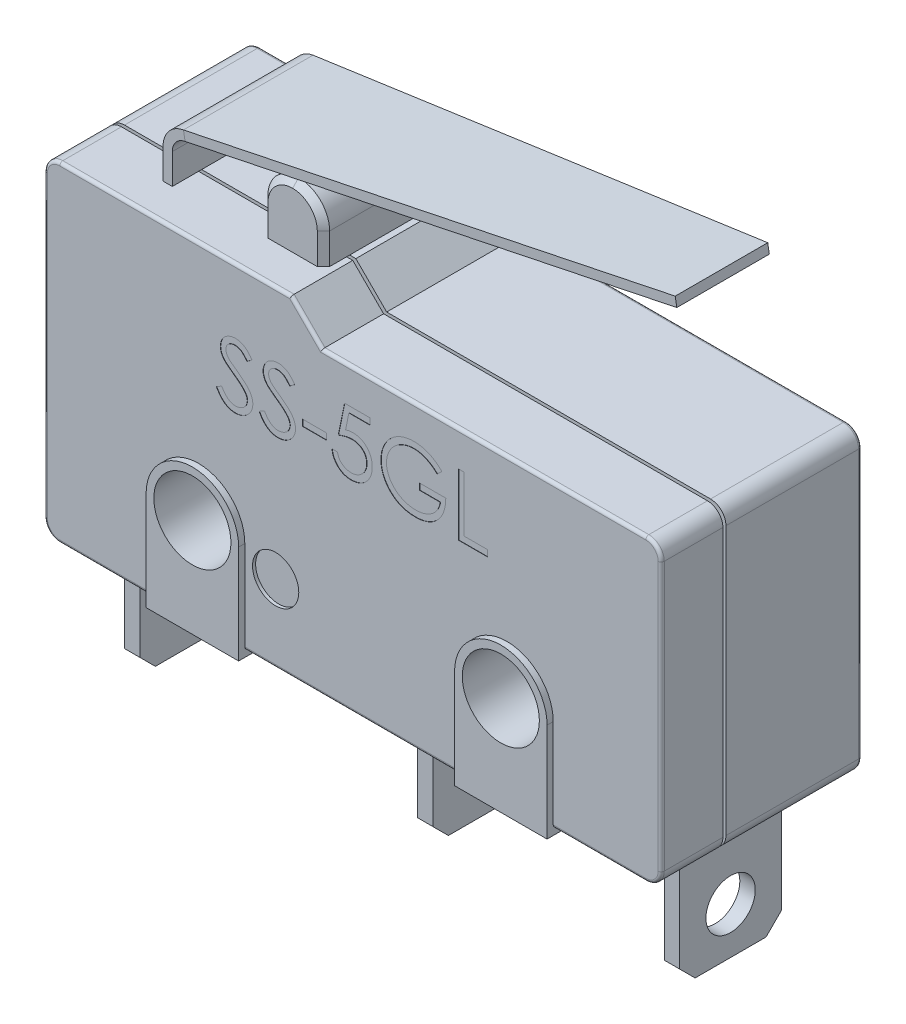
SolidWorks part; units mm, degrees
ref_plane "前基準面" through (0, 0, 0) normal (0, 0, 1) x (1, 0, 0)
ref_plane "上基準面" through (0, 0, 0) normal (0, 1, 0) x (1, 0, 0)
ref_plane "右基準面" through (0, 0, 0) normal (1, 0, 0) x (0, 0, -1)
sketch "草圖1" plane through (0, 0, 0) normal (0, 0, 1) x (1, 0, 0)
  line L0 (9, 9.7) -> (8, 10.7)
  line L1 (0, 0) -> (20, 0)
  line L2 (0, 0) -> (0, 10.7)
  line L3 (0, 10.7) -> (8, 10.7)
  line L4 (20, 0) -> (20, 10.7)
  line L7 (9, 9.7) -> (20, 9.7)
  line L8 (20, 10.7) -> (20, 9.7)
  dimension "D1" = 20
  dimension "D2" = 10.7
  dimension "D3" = 1
  dimension "D4" = 9
  dimension "D5" = 135
extrude "填料-伸長1" add sketch "草圖1" along normal blind 6.5 contours L7 L0 L3 L2 L1 L4 region at (9.7588, 5.0742, 0)
sketch "草圖2" plane through (0, 0, 6.5) normal (0, 0, 1) x (1, 0, 0)
  line L0 (0, 0) -> (0, 10.7) construction
  line L1 (0, 0) -> (20, 0) construction
  circle A0 centre (5, 3) radius 1.25
  circle A1 centre (15, 3) radius 1.25
  dimension "D1" = 2.5
  dimension "D2" = 10
  dimension "D3" = 5
  dimension "D4" = 3
extrude "除料-伸長1" cut sketch "草圖2" against normal through all
sketch "草圖3" plane through (0, 0, 6.5) normal (0, 0, 1) x (1, 0, 0)
  line L0 (0, 0) -> (20, 0) construction
  line L2 (3.5, 3) -> (3.5, 0)
  line L3 (3.5, 0) -> (6.5, 0)
  line L4 (6.5, 3) -> (6.5, 0)
  line L7 (13.5, 3) -> (13.5, 0)
  line L8 (13.5, 0) -> (16.5, 0)
  line L9 (16.5, 3) -> (16.5, 0)
  arc A0 (6.5, 3) -> (3.5, 3) centre (5, 3) ccw
  arc A1 (16.5, 3) -> (13.5, 3) centre (15, 3) ccw
  circle A2 centre (5, 3) radius 1.25
  circle A3 centre (15, 3) radius 1.25
  dimension "D1" = 3
  dimension "D2" = 2.5
extrude "填料-伸長2" add sketch "草圖3" along normal blind 0.2
sketch "草圖4" plane through (0, 0, 0) normal (0, 0, -1) x (-1, 0, 0)
  line L0 (0, 0) -> (-20, 0) construction
  line L2 (-16.5, 3) -> (-16.5, 0)
  line L3 (-16.5, 0) -> (-13.5, 0)
  line L4 (-13.5, 3) -> (-13.5, 0)
  line L6 (-6.5, 3) -> (-6.5, 0)
  line L7 (-6.5, 0) -> (-3.5, 0)
  line L8 (-3.5, 3) -> (-3.5, 0)
  arc A0 (-13.5, 3) -> (-16.5, 3) centre (-15, 3) ccw
  arc A1 (-3.5, 3) -> (-6.5, 3) centre (-5, 3) ccw
  circle A2 centre (-15, 3) radius 1.25
  circle A3 centre (-5, 3) radius 1.25
  dimension "D1" = 3
  dimension "D2" = 2.5
extrude "填料-伸長3" add sketch "草圖4" along normal blind 0.2
sketch "草圖5" plane through (0, 10.7, 0) normal (0, 1, 0) x (1, 0, 0)
  line L0 (0, -6.5) -> (0, 0) construction
  line L1 (5.8, -1.25) -> (7.8, -1.25)
  line L2 (5.8, -1.25) -> (5.8, -5.25)
  line L3 (5.8, -5.25) -> (7.8, -5.25)
  line L4 (7.8, -1.25) -> (7.8, -5.25)
  line L5 (0, 0) -> (8, 0) construction
  dimension "D1" = 2
  dimension "D2" = 5.8
  dimension "D3" = 4
  dimension "D4" = 1.25
extrude "填料-伸長4" add sketch "草圖5" along normal blind 2 separate body
fillet "圓角1" radius 1 2 edges at (5.8, 12.7, 3.25) (7.8, 12.7, 3.25)
ref_plane "平面1" through (0, 0, 5.35) normal (0, 0, 1) x (1, 0, 0)
sketch "草圖6" plane through (0, 0, 5.35) normal (0, 0, 1) x (1, 0, 0)
  line L0 (3, 10.7) -> (3, 11.6805)
  line L1 (0, 10.7) -> (8, 10.7) construction
  line L2 (3.4132, 12.1729) -> (18.7569, 14.8784)
  line L3 (0, 0) -> (0, 10.7) construction
  line L4 (2.7, 10.7) -> (2.7, 11.6805)
  line L5 (3.3611, 12.4683) -> (18.7048, 15.1738)
  line L6 (18.7569, 14.8784) -> (18.7048, 15.1738)
  line L7 (3, 10.7) -> (2.7, 10.7)
  arc A0 (3, 11.6805) -> (3.4132, 12.1729) centre (3.5, 11.6805) cw
  arc A1 (2.7, 11.6805) -> (3.3611, 12.4683) centre (3.5, 11.6805) cw
  point P7 (3, 12.1)
  dimension "D3" = 0.5
  dimension "D1" = 16
  dimension "D2" = 1.4
  dimension "D4" = 3
  dimension "D5" = 100
  dimension "D6" = 0.3
extrude "填料-伸長5" add sketch "草圖6" against normal blind 4.2 separate body
sketch "草圖7" plane through (-2.0309, 11.5176, 0) normal (-0.1736, 0.9848, 0) x (0.9848, 0.1736, 0)
  line L0 (21.0556, -1.15) -> (21.0556, -1.75)
  line L1 (21.0556, -1.15) -> (21.0556, -5.35) construction
  line L2 (21.0556, -1.75) -> (5.4751, -1.15)
  line L3 (5.4751, -1.15) -> (21.0556, -1.15)
  line L4 (21.0556, -4.75) -> (21.0556, -5.35)
  line L5 (21.0556, -5.35) -> (5.4751, -5.35)
  line L6 (-5.885, -5.35) -> (5.885, -5.35) construction
  line L7 (5.4751, -5.35) -> (21.0556, -4.75)
  dimension "D1" = 0.6
  dimension "D2" = 0.6
extrude "除料-伸長2" cut sketch "草圖7" against normal up to next (0.3 mm away)
sketch "草圖8" plane through (0, 0, 0) normal (0, -1, 0) x (1, 0, 0)
  line L0 (0, 6.5) -> (3.5, 6.5) construction
  line L1 (1, 4.9) -> (1.5, 4.9)
  line L2 (1, 4.9) -> (1, 1.6)
  line L3 (1, 1.6) -> (1.5, 1.6)
  line L4 (1.5, 4.9) -> (1.5, 1.6)
  line L6 (0, 6.5) -> (0, 0) construction
  line L7 (20, 6.5) -> (20, 0) construction
  line L8 (10.5, 4.9) -> (11, 4.9)
  line L9 (10.5, 4.9) -> (10.5, 1.6)
  line L10 (10.5, 1.6) -> (11, 1.6)
  line L11 (11, 4.9) -> (11, 1.6)
  line L12 (18.5, 4.9) -> (19, 4.9)
  line L13 (18.5, 4.9) -> (18.5, 1.6)
  line L14 (18.5, 1.6) -> (19, 1.6)
  line L15 (19, 4.9) -> (19, 1.6)
  dimension "D1" = 3.3
  dimension "D2" = 0.5
  dimension "D3" = 1.6
  dimension "D4" = 1
  dimension "D5" = 0.5
  dimension "D6" = 0.5
  dimension "D7" = 1
  dimension "D8" = 9
extrude "填料-伸長6" add sketch "草圖8" along normal blind 4 separate body
sketch "草圖9" plane through (1, 0, 0) normal (-1, 0, 0) x (0, 0, 1)
  line L0 (1.6, -4) -> (1.6, 0) construction
  line L2 (4.9, -4) -> (1.6, -4) construction
  circle A0 centre (3.25, -2.5) radius 0.8
  dimension "D1" = 1.6
  dimension "D2" = 1.65
  dimension "D3" = 1.5
extrude "除料-伸長3" cut sketch "草圖9" against normal through all
sketch "草圖11" plane through (1, 0, 0) normal (-1, 0, 0) x (0, 0, 1)
  line L0 (1.6, -3.5) -> (2.1, -4)
  line L1 (1.6, -4) -> (1.6, 0) construction
  line L2 (4.9, -4) -> (1.6, -4) construction
  line L3 (2.1, -4) -> (1.6, -4)
  line L4 (1.6, -4) -> (1.6, -3.5)
  line L5 (4.9, -3.5) -> (4.4, -4)
  line L6 (4.9, -4) -> (4.9, 0) construction
  line L7 (4.4, -4) -> (4.9, -4)
  line L8 (4.9, -4) -> (4.9, -3.5)
  dimension "D1" = 0.5
  dimension "D2" = 0.5
  dimension "D3" = 0.5
  dimension "D4" = 0.5
extrude "除料-伸長4" cut sketch "草圖11" against normal through all
sketch "草圖12" plane through (0, 0, 0) normal (0, -1, 0) x (1, 0, 0)
  line L0 (16.5, -0.2) -> (16.5, 0) construction
  line L1 (3.5, 6.7) -> (6.5, 6.7)
  line L2 (3.5, 6.7) -> (3.5, -0.2)
  line L3 (3.5, -0.2) -> (6.5, -0.2)
  line L4 (6.5, 6.7) -> (6.5, -0.2)
  line L5 (13.5, 6.7) -> (16.5, 6.7)
  line L6 (13.5, 6.7) -> (13.5, -0.2)
  line L7 (13.5, -0.2) -> (16.5, -0.2)
  line L8 (16.5, 6.7) -> (16.5, -0.2)
extrude "填料-伸長7" add sketch "草圖12" along normal blind 0.2
fillet "圓角2" radius 0.5 4 edges at (20, 0, 3.25) (20, 9.7, 3.25) (0, 0, 3.25) (0, 10.7, 3.25)
sketch "草圖13" plane through (0, 0, 6.5) normal (0, 0, 1) x (1, 0, 0)
  text T0 "SS-5GL" font "Century Gothic" height 2
extrude "除料-伸長5" cut sketch "草圖13" against normal blind 0.01
chamfer "導角2" distance 0.2 angle 45 8 edges at (5.8, 11.2, 1.25) (6.0929, 12.4071, 1.25) (7.5071, 12.4071, 1.25) (7.8, 11.2, 1.25) (5.8, 11.2, 5.25) (6.0929, 12.4071, 5.25) (7.5071, 12.4071, 5.25) (7.8, 11.2, 5.25)
fillet "圓角3" radius 0.1 20 edges at (10, 0, 0) (0.1464, 0.1464, 0) (0, 5.35, 0) (0.1464, 10.5536, 0) (19.8536, 0.1464, 0) (20, 4.85, 0) (19.8536, 9.5536, 0) (10, 0, 6.5) (19.8536, 0.1464, 6.5) (20, 4.85, 6.5) (19.8536, 9.5536, 6.5) (0.1464, 0.1464, 6.5) (0, 5.35, 6.5) (0.1464, 10.5536, 6.5) (4.25, 10.7, 0) (8.5, 10.2, 0) (14.25, 9.7, 0) (14.25, 9.7, 6.5) (8.5, 10.2, 6.5) (4.25, 10.7, 6.5)
sketch "草圖14" plane through (0, 0, 6.5) normal (0, 0, 1) x (1, 0, 0)
  line L1 (0, 0.5) -> (0, 10.2) construction
  line L2 (3.5, 0) -> (0.5, 0) construction
  circle A0 centre (7.5, 2.5) radius 0.75
  dimension "D1" = 1.5
  dimension "D2" = 7.5
  dimension "D3" = 2.5
extrude "除料-伸長6" cut sketch "草圖14" against normal blind 0.1
sketch "草圖15" plane through (0, 0, 0) normal (0, 0, -1) x (-1, 0, 0)
  line L0 (0, 10.2) -> (0, 0.5) construction
  line L1 (-0.5, 0) -> (-3.5, 0) construction
  circle A0 centre (-7.5, 2.5) radius 0.75
  dimension "D1" = 1.5
  dimension "D2" = 7.5
  dimension "D3" = 2.5
extrude "除料-伸長7" cut sketch "草圖15" against normal blind 0.1
ref_plane "平面4" through (0, 0, 4.5) normal (0, 0, 1) x (1, 0, 0)
sketch "草圖18" plane through (0, 0, 4.5) normal (0, 0, 1) x (1, 0, 0)
  line L0 (7.8, 10.7) -> (5.8, 10.7)
  line L1 (7.8, 11.125) -> (7.8, 10.7)
  line L2 (5.8, 10.7) -> (5.8, 11.125)
  line L3 (5.8, 11.125) -> (7.8, 11.125)
  line L4 (5.8, 11.125) -> (7.8, 11.125)
  line L5 (5.8, 10.7) -> (5.8, 11.125)
  line L6 (7.8, 11.125) -> (7.8, 10.7)
  line L7 (7.8, 10.7) -> (5.8, 10.7)
  line L8 (2.7, 11.125) -> (3, 11.125)
  line L9 (2.7, 10.7) -> (3, 10.7)
  line L10 (3, 10.7) -> (3, 11.125)
  line L11 (2.7, 11.125) -> (2.7, 10.7)
  line L12 (2.7, 11.125) -> (2.7, 10.7)
  line L13 (3, 10.7) -> (3, 11.125)
  line L14 (2.7, 10.7) -> (3, 10.7)
  line L15 (2.7, 11.125) -> (3, 11.125)
  line L16 (1, 0) -> (1.5, 0)
  line L17 (1.5, 0) -> (1.5, -0.425)
  line L18 (1, -0.425) -> (1, 0)
  line L19 (1.5, -0.425) -> (1, -0.425)
  line L20 (1.5, -0.425) -> (1, -0.425)
  line L21 (1, -0.425) -> (1, 0)
  line L22 (1.5, 0) -> (1.5, -0.425)
  line L23 (1, 0) -> (1.5, 0)
  line L24 (10.5, 0) -> (11, 0)
  line L25 (11, 0) -> (11, -0.425)
  line L26 (10.5, -0.425) -> (10.5, 0)
  line L27 (11, -0.425) -> (10.5, -0.425)
  line L28 (11, -0.425) -> (10.5, -0.425)
  line L29 (10.5, -0.425) -> (10.5, 0)
  line L30 (11, 0) -> (11, -0.425)
  line L31 (10.5, 0) -> (11, 0)
  line L32 (18.5, 0) -> (19, 0)
  line L33 (19, 0) -> (19, -0.425)
  line L34 (18.5, -0.425) -> (18.5, 0)
  line L35 (19, -0.425) -> (18.5, -0.425)
  line L36 (19, -0.425) -> (18.5, -0.425)
  line L37 (18.5, -0.425) -> (18.5, 0)
  line L38 (19, 0) -> (19, -0.425)
  line L39 (18.5, 0) -> (19, 0)
  line L40 (13.5, 0) -> (6.5, 0)
  line L41 (19.5, 0) -> (16.5, 0)
  line L42 (3.5, 0) -> (0.5, 0)
  line L43 (3.5, -0.2) -> (3.5, 0)
  line L44 (6.5, 0) -> (6.5, -0.2)
  line L45 (3.5, -0.2) -> (6.5, -0.2)
  line L46 (19.5, 9.7) -> (9, 9.7)
  line L47 (20, 9.2) -> (20, 0.5)
  line L48 (8, 10.7) -> (9, 9.7)
  line L49 (8, 10.7) -> (0.5, 10.7)
  line L50 (0, 10.2) -> (0, 0.5)
  line L51 (13.5, -0.2) -> (13.5, 0)
  line L52 (16.5, 0) -> (16.5, -0.2)
  line L53 (13.5, -0.2) -> (16.5, -0.2)
  line L54 (13.5, -0.2) -> (16.5, -0.2)
  line L55 (16.5, 0) -> (16.5, -0.2)
  line L56 (13.5, -0.2) -> (13.5, 0)
  line L57 (0, 10.2) -> (0, 0.5)
  line L58 (8, 10.7) -> (0.5, 10.7)
  line L59 (8, 10.7) -> (9, 9.7)
  line L60 (20, 9.2) -> (20, 0.5)
  line L61 (19.5, 9.7) -> (9, 9.7)
  line L62 (3.5, -0.2) -> (6.5, -0.2)
  line L63 (6.5, 0) -> (6.5, -0.2)
  line L64 (3.5, -0.2) -> (3.5, 0)
  line L65 (3.5, 0) -> (0.5, 0)
  line L66 (19.5, 0) -> (16.5, 0)
  line L67 (13.5, 0) -> (6.5, 0)
  line L68 (19.5, 9.5) -> (8.9172, 9.5)
  line L69 (7.9172, 10.5) -> (8.9172, 9.5)
  line L70 (7.9172, 10.5) -> (0.5, 10.5)
  line L71 (0.2, 10.2) -> (0.2, 0.5)
  line L72 (3.7, 0.2) -> (0.5, 0.2)
  line L73 (3.7, 0) -> (3.7, 0.2)
  line L74 (3.7, 0) -> (6.3, 0)
  line L75 (6.3, 0.2) -> (6.3, 0)
  line L76 (13.7, 0.2) -> (6.3, 0.2)
  line L77 (13.7, 0) -> (13.7, 0.2)
  line L78 (13.7, 0) -> (16.3, 0)
  line L79 (16.3, 0.2) -> (16.3, 0)
  line L80 (19.5, 0.2) -> (16.3, 0.2)
  line L81 (19.8, 9.2) -> (19.8, 0.5)
  circle A0 centre (15, 3) radius 1.25
  circle A1 centre (5, 3) radius 1.25
  arc A2 (20, 9.2) -> (19.5, 9.7) centre (19.5, 9.2) ccw
  arc A3 (19.5, 0) -> (20, 0.5) centre (19.5, 0.5) ccw
  arc A4 (0.5, 10.7) -> (0, 10.2) centre (0.5, 10.2) ccw
  arc A5 (0, 0.5) -> (0.5, 0) centre (0.5, 0.5) ccw
  arc A6 (0, 0.5) -> (0.5, 0) centre (0.5, 0.5) ccw
  arc A7 (0.5, 10.7) -> (0, 10.2) centre (0.5, 10.2) ccw
  arc A8 (19.5, 0) -> (20, 0.5) centre (19.5, 0.5) ccw
  arc A9 (20, 9.2) -> (19.5, 9.7) centre (19.5, 9.2) ccw
  arc A10 (0.5, 10.5) -> (0.2, 10.2) centre (0.5, 10.2) ccw
  arc A11 (0.2, 0.5) -> (0.5, 0.2) centre (0.5, 0.5) ccw
  arc A12 (19.5, 0.2) -> (19.8, 0.5) centre (19.5, 0.5) ccw
  arc A13 (19.8, 9.2) -> (19.5, 9.5) centre (19.5, 9.2) ccw
  circle A18 centre (5, 3) radius 1.25
  circle A19 centre (15, 3) radius 1.25
extrude "除料-伸長8" cut sketch "草圖18" against normal blind 0.1 contours A13 L81 A12 L80 L79 L78 L77 L76 L75 L74 L73 L72 A11 L71 A10 L70 L69 L68 region at (7.9, 10.6772, 4.5)
